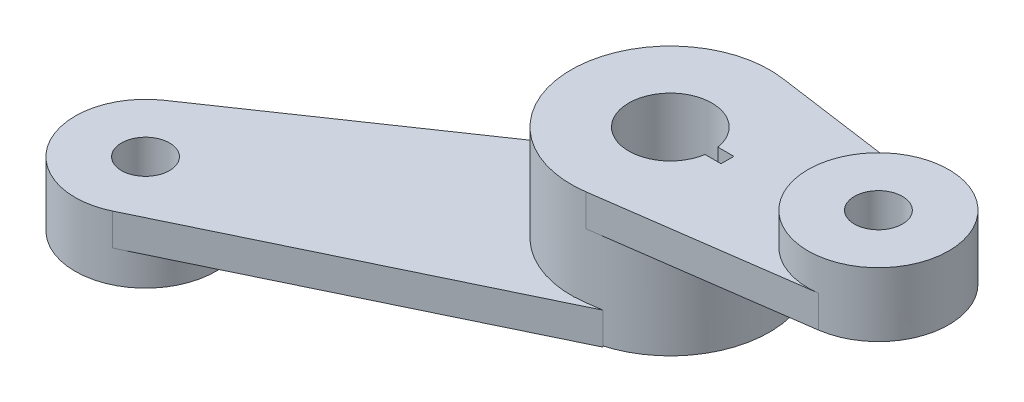
SolidWorks part; units mm, degrees
ref_plane "Front Plane" through (0, 0, 0) normal (0, 0, 1) x (1, 0, 0)
ref_plane "Top Plane" through (0, 0, 0) normal (0, 1, 0) x (1, 0, 0)
ref_plane "Right Plane" through (0, 0, 0) normal (1, 0, 0) x (0, 0, -1)
sketch "Sketch1" plane through (0, 0, 0) normal (0, 1, 0) x (1, 0, 0)
  line L0 (9.0835, -30.0315) -> (-94.383, -79.8239)
  line L1 (-17.4699, 25.6087) -> (-116.321, -41.8261)
  line L2 (4.2923, -30.7014) -> (68.0462, -21.7881)
  line L3 (68.0462, 21.7881) -> (4.2923, 30.7014)
  line L4 (0, 0) -> (-103.923, -60) construction
  line L5 (0, 0) -> (91.9117, 0) construction
  line L6 (12.8452, 2) -> (17.8452, 2)
  line L7 (17.8452, 2) -> (17.8452, -2)
  line L8 (17.8452, -2) -> (12.8452, -2)
  arc A0 (12.8452, 2) -> (12.8452, -2) centre (0, 0) ccw
  circle A1 centre (0, 0) radius 22
  circle A2 centre (0, 0) radius 31
  circle A3 centre (65, 0) radius 7.5
  circle A4 centre (65, 0) radius 22
  circle A5 centre (-103.923, -60) radius 7.5
  circle A6 centre (-103.923, -60) radius 22
  point P10 (31, 0)
  point P11 (0, 0)
  point P24 (12.8452, -2)
  point P25 (12.8452, 2)
  point P26 (0, 0)
  point P27 (4.813, -30.7014)
  point P28 (0, 0)
  point P30 (0, 0)
  point P31 (-115.7284, -41.4218)
  point P32 (0, 0)
  dimension "D1" = 65
  dimension "D2" = 44
  dimension "D3" = 15
  dimension "D4" = 44
  dimension "D5" = 15
  dimension "D7" = 62
  dimension "D8" = 44
  dimension "D9" = 26
  dimension "D6" = 120
  dimension "D10" = 30
  dimension "D11" = 4
  dimension "D12" = 5
extrude "Boss-Extrude1" add sketch "Sketch1" along normal blind 40 contours A1 A0 L6 L7 L8 | A2 A1 region at (-28.0978, 0, 10.859) region at (-21.3777, 0, 0)
extrude "Boss-Extrude2" add sketch "Sketch1<3>" along normal blind 10 from offset 30 contours A4 L3 A2 L2 region at (36.83, 0, 0)
sketch "Sketch1<3>" plane through (0, 0, 0) normal (0, 1, 0) x (1, 0, 0) same geometry as "Sketch1"
extrude "Boss-Extrude3" add sketch "Sketch1<4>" along normal blind 20 from offset 30 contours A4 A3 region at (43.6223, 0, 0)
sketch "Sketch1<4>" plane through (0, 0, 0) normal (0, 1, 0) x (1, 0, 0) same geometry as "Sketch1"
extrude "Boss-Extrude4" add sketch "Sketch1<5>" along normal blind 10 contours A6 L0 L2 A2 L1 region at (-54.2031, 0, 31.2839)
sketch "Sketch1<5>" plane through (0, 0, 0) normal (0, 1, 0) x (1, 0, 0) same geometry as "Sketch1"
extrude "Boss-Extrude5" add sketch "Sketch1<6>" against normal blind 20 from offset 10 contours A6 A5 region at (-122.4367, 0, 70.6889)
sketch "Sketch1<6>" plane through (0, 0, 0) normal (0, 1, 0) x (1, 0, 0) same geometry as "Sketch1"
